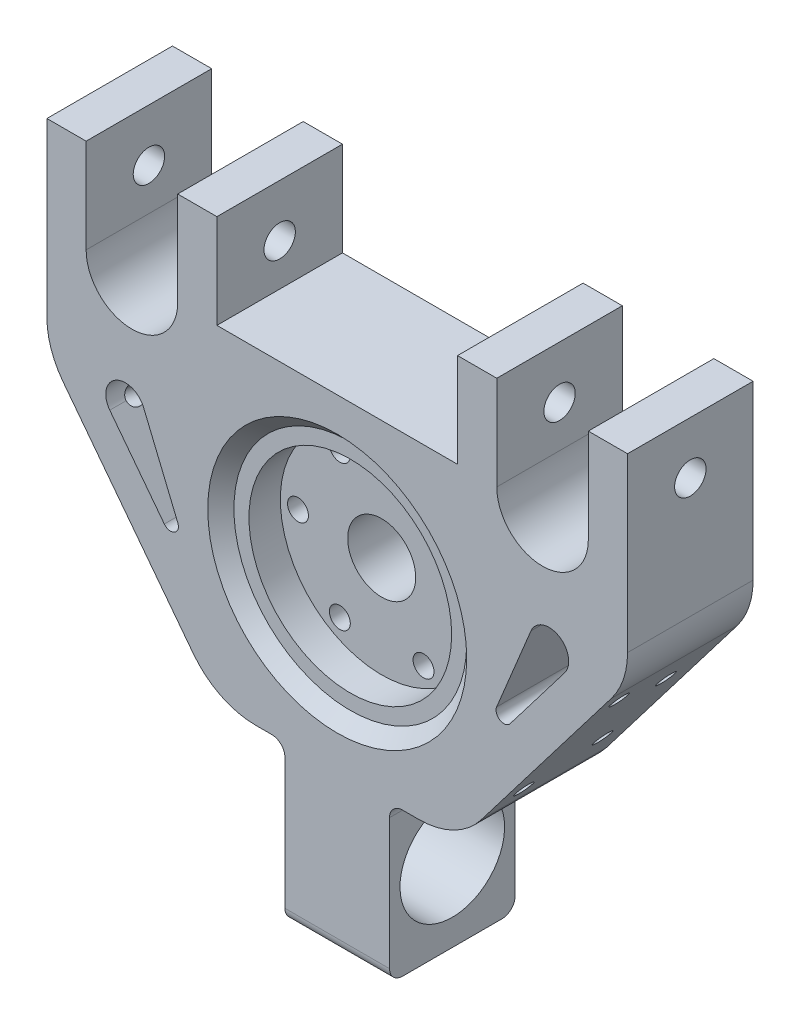
SolidWorks part; units mm, degrees
material "7075-O (SS)"
ref_plane "Płaszczyzna przednia" through (0, 0, 0) normal (0, 0, 1) x (1, 0, 0)
ref_plane "Płaszczyzna górna" through (0, 0, 0) normal (0, 1, 0) x (1, 0, 0)
ref_plane "Płaszczyzna prawa" through (0, 0, 0) normal (1, 0, 0) x (0, 0, -1)
sketch "Szkic1" plane through (0, 0, 0) normal (0, 0, 1) x (1, 0, 0)
  line L1 (-111, -62.5) -> (111, -62.5)
  line L2 (-111, -62.5) -> (-111, 62.5)
  line L3 (-111, 62.5) -> (111, 62.5)
  line L4 (111, -62.5) -> (111, 62.5)
  line L5 (-111, -62.5) -> (111, 62.5) construction
  line L6 (-111, 62.5) -> (111, -62.5) construction
  circle A0 centre (0, 0) radius 13
  circle A1 centre (-32, 0) radius 4
  circle A2 centre (-16, 27.7128) radius 4
  circle A3 centre (16, 27.7128) radius 4
  circle A4 centre (32, 0) radius 4
  circle A5 centre (16, -27.7128) radius 4
  circle A6 centre (-16, -27.7128) radius 4
  point P0 (0, 0)
  point P22 (0, 0)
  point P23 (0, 0)
  dimension "D3" = 26
  dimension "D4" = 8
  dimension "D5" = 32
  dimension "D2" = 222
  dimension "12" = 125
  dimension "D9" = 32
  dimension "D6" = 6
extrude "Dodanie-wyciągnięcie1" add sketch "Szkic1" along normal blind 13.5 and the other way blind 13.5
sketch "Szkic4" plane through (0, 62.5, 0) normal (0, 1, 0) x (1, 0, 0)
  line L0 (111, -13.5) -> (-111, -13.5) construction
  line L1 (-111, 13.5) -> (-96, 13.5)
  line L2 (-111, 13.5) -> (-111, -13.5)
  line L3 (-111, -13.5) -> (-96, -13.5)
  line L4 (-96, 13.5) -> (-96, -13.5)
  line L5 (111, 13.5) -> (-111, 13.5) construction
  line L6 (-61, 13.5) -> (-46, 13.5)
  line L7 (-61, 13.5) -> (-61, -13.5)
  line L8 (-61, -13.5) -> (-46, -13.5)
  line L9 (-46, 13.5) -> (-46, -13.5)
  line L11 (46, 13.5) -> (61, 13.5)
  line L12 (46, 13.5) -> (46, -13.5)
  line L13 (46, -13.5) -> (61, -13.5)
  line L14 (61, 13.5) -> (61, -13.5)
  line L15 (111, 13.5) -> (96, 13.5)
  line L16 (111, 13.5) -> (111, -13.5)
  line L17 (111, -13.5) -> (96, -13.5)
  line L18 (96, 13.5) -> (96, -13.5)
  dimension "D1" = 15
  dimension "D2" = 15
  dimension "D3" = 15
  dimension "D4" = 15
  dimension "D5" = 35
  dimension "D6" = 35
extrude "Dodanie-wyciągnięcie4" add sketch "Szkic4" along normal blind 36
sketch "Szkic13" plane through (0, 0, 13.5) normal (0, 0, 1) x (1, 0, 0)
  circle A0 centre (0, 0) radius 38.75
  circle A1 centre (0, 0) radius 13 construction
  dimension "D1" = 77.5
extrude "Wytnij-wyciągnięcie4" cut sketch "Szkic13" against normal blind 17 contours A0
sketch "Szkic15" plane through (0, 0, 13.5) normal (0, 0, 1) x (1, 0, 0)
  circle A0 centre (0, 0) radius 44.5
  circle A1 centre (0, 0) radius 38.75 construction
  dimension "D1" = 89
extrude "Wytnij-wyciągnięcie5" cut sketch "Szkic15" against normal blind 5
draft "Pochylenie1" type of draft neutral plane draft angle 45 faces to draft 1 face at (44.5, 0, 8.5) neutral plane through (0, 0, 8.5) neutral plane normal (0, 0, 1) parameters "D1"=45
sketch "Szkic16" plane through (0, 0, -13.5) normal (0, 0, -1) x (-1, 0, 0)
  line L18 (-111, 98.5) -> (-111, -62.5)
  line L19 (-111, -62.5) -> (111, -62.5)
  line L22 (111, -62.5) -> (111, 98.5)
  line L23 (111, 98.5) -> (96, 98.5)
  line L24 (96, 98.5) -> (96, 62.5)
  line L25 (96, 62.5) -> (61, 62.5)
  line L26 (61, 62.5) -> (61, 98.5)
  line L27 (61, 98.5) -> (46, 98.5)
  line L28 (46, 98.5) -> (46, 62.5)
  line L29 (46, 62.5) -> (-46, 62.5)
  line L30 (-46, 62.5) -> (-46, 98.5)
  line L31 (-46, 98.5) -> (-61, 98.5)
  line L32 (-61, 98.5) -> (-61, 62.5)
  line L33 (-61, 62.5) -> (-96, 62.5)
  line L34 (-96, 62.5) -> (-96, 98.5)
  line L35 (-96, 98.5) -> (-111, 98.5)
  line L36 (-111, 98.5) -> (-111, -62.5)
  line L37 (-111, -62.5) -> (111, -62.5)
  line L40 (111, -62.5) -> (111, 98.5)
  line L41 (111, 98.5) -> (96, 98.5)
  line L42 (96, 98.5) -> (96, 62.5)
  line L43 (96, 62.5) -> (61, 62.5)
  line L44 (61, 62.5) -> (61, 98.5)
  line L45 (61, 98.5) -> (46, 98.5)
  line L46 (46, 98.5) -> (46, 62.5)
  line L47 (46, 62.5) -> (-46, 62.5)
  line L48 (-46, 62.5) -> (-46, 98.5)
  line L49 (-46, 98.5) -> (-61, 98.5)
  line L50 (-61, 98.5) -> (-61, 62.5)
  line L51 (-61, 62.5) -> (-96, 62.5)
  line L52 (-96, 62.5) -> (-96, 98.5)
  line L53 (-96, 98.5) -> (-111, 98.5)
  circle A1 centre (0, 0) radius 13
  circle A2 centre (0, 0) radius 13
  circle A3 centre (32, 0) radius 4
  circle A4 centre (32, 0) radius 4
  circle A5 centre (16, 27.7128) radius 4
  circle A6 centre (16, 27.7128) radius 4
  circle A7 centre (-16, 27.7128) radius 4
  circle A8 centre (-16, 27.7128) radius 4
  circle A9 centre (-32, 0) radius 4
  circle A10 centre (-32, 0) radius 4
  circle A11 centre (-16, -27.7128) radius 4
  circle A12 centre (-16, -27.7128) radius 4
  circle A13 centre (16, -27.7128) radius 4
  circle A14 centre (16, -27.7128) radius 4
  dimension "D1" = 0
  dimension "D2" = 0
  dimension "D3" = 0
  dimension "D4" = 0
  dimension "D5" = 0
  dimension "D6" = 0
  dimension "D7" = 0
  dimension "D8" = 0
extrude "Dodanie-wyciągnięcie6" add sketch "Szkic16" along normal blind 21
sketch "Szkic5" plane through (-111, 0, 0) normal (-1, 0, 0) x (0, 0, 1)
  line L0 (13.5, 98.5) -> (13.5, -62.5) construction
  line L2 (-34.5, 98.5) -> (13.5, 98.5) construction
  circle A0 centre (-10.5, 78.5) radius 6
  dimension "D1" = 12
  dimension "D2" = 24
  dimension "D3" = 20
extrude "Wytnij-wyciągnięcie3" cut sketch "Szkic5" against normal through all contours A0
sketch "Szkic18" plane through (0, 0, -34.5) normal (0, 0, -1) x (-1, 0, 0)
  line L2 (111, 22.5) -> (46, -62.5)
  line L3 (111, -62.5) -> (111, 98.5) construction
  line L4 (-111, -62.5) -> (111, -62.5) construction
  line L5 (111, 22.5) -> (111, -62.5)
  line L6 (111, -62.5) -> (46, -62.5)
  line L7 (-111, -62.5) -> (-46, -62.5)
  line L8 (-46, -62.5) -> (-111, 22.5)
  line L9 (-111, 98.5) -> (-111, -62.5) construction
  line L10 (-111, 22.5) -> (-111, -62.5)
  dimension "D1" = 65
  dimension "D2" = 85
extrude "Wytnij-wyciągnięcie6" cut sketch "Szkic18" against normal through all
fillet "Zaokrąglenie1" radius 30 1 edges at (-111, 22.5, -10.5)
fillet "Zaokrąglenie2" radius 30 3 edges at (111, 22.5, -10.5) (46, -62.5, -10.5) (-46, -62.5, -10.5)
sketch "Szkic19" plane through (0, 0, -34.5) normal (0, 0, -1) x (-1, 0, 0)
  line L5 (-31.1748, -62.5) -> (31.1748, -62.5) construction
  line L6 (-20, -62.5) -> (20, -62.5)
  line L7 (-20, -62.5) -> (-20, -122.5)
  line L8 (-20, -122.5) -> (20, -122.5)
  line L9 (20, -62.5) -> (20, -122.5)
  point P4 (0, -62.5)
  dimension "D1" = 40
  dimension "D2" = 60
extrude "Dodanie-wyciągnięcie7" add sketch "Szkic19" against normal up to surface (48 mm away) up to face at (-49.5, 0, 13.5)
sketch "Szkic23" plane through (20, 0, 0) normal (1, 0, 0) x (0, 0, -1)
  line L0 (-13.5, -122.5) -> (34.5, -122.5) construction
  circle A0 centre (10.5, -92.5) radius 20
  point P5 (10.5, -122.5)
  dimension "D1" = 40
  dimension "D2" = 30
extrude "Wytnij-wyciągnięcie7" cut sketch "Szkic23" against normal up to next
sketch "Szkic24" plane through (0, 0, -34.5) normal (0, 0, -1) x (-1, 0, 0)
  line L0 (-96, 62.5) -> (-61, 62.5)
  line L1 (61, 62.5) -> (96, 62.5)
  line L2 (-96, 62.5) -> (-96, 98.5) construction
  line L3 (61, 62.5) -> (61, 98.5) construction
  arc A0 (-96, 62.5) -> (-61, 62.5) centre (-78.5, 62.5) ccw
  arc A1 (61, 62.5) -> (96, 62.5) centre (78.5, 62.5) ccw
extrude "Wytnij-wyciągnięcie8" cut sketch "Szkic24" against normal up to next
fillet "Zaokrąglenie4" radius 5 2 edges at (20, -62.5, -10.5) (-20, -62.5, -10.5)
fillet "Zaokrąglenie5" radius 5 2 edges at (0, -122.5, -34.5) (0, -122.5, 13.5)
sketch "Szkic25" plane through (0, 0, 13.5) normal (0, 0, 1) x (1, 0, 0)
  line L0 (-60.9515, -10.3535) -> (-74.0693, 21.3662)
  line L1 (-66.1069, -13.3224) -> (-86.9577, 13.9441)
  line L2 (0, 0) -> (0, 65.4939) construction
  line L3 (66.1069, -13.3224) -> (86.9577, 13.9441)
  line L4 (-111, 98.5) -> (-111, 32.656) construction
  line L5 (-61, 98.5) -> (-46, 98.5) construction
  line L6 (60.9515, -10.3535) -> (74.0693, 21.3662)
  line L7 (-104.8307, 14.4325) -> (-55.0056, -50.7235) construction
  arc A0 (-74.0693, 21.3662) -> (-86.9577, 13.9441) centre (-81, 18.5) ccw
  arc A13 (-66.1069, -13.3224) -> (-60.9515, -10.3535) centre (-63.7238, -11.5) ccw
  arc A14 (66.1069, -13.3224) -> (60.9515, -10.3535) centre (63.7238, -11.5) cw
  arc A15 (74.0693, 21.3662) -> (86.9577, 13.9441) centre (81, 18.5) cw
  dimension "D1" = 30
  dimension "D2" = 80
  dimension "D6" = 6
  dimension "D5" = 15
  dimension "D4" = 110
extrude "Wytnij-wyciągnięcie9" cut sketch "Szkic25" against normal up to surface (48 mm away) up to face at (0, 17.7221, -34.5)
hole_wizard "Otwór gwintowany M81" positions "Szkic27" profile "Szkic28" tap size "M8" standard "ISO"
sketch "Szkic27" plane through (-59.1845, -45.2587, 0) normal (-0.7944, -0.6075, 0) x (0, 0, 1)
  line L0 (-34.5, 75.144) -> (-34.5, -6.8795) construction
  line L1 (-10.5, 22.8237) -> (-10.5, 73.239) construction
  line L3 (16.7871, 34.1323) -> (-56.7075, 34.1323) construction
  line L5 (13.5, 75.144) -> (13.5, -6.8795) construction
  line L6 (13.5, 75.144) -> (-34.5, 75.144) construction
  line L7 (-34.5, -6.8795) -> (13.5, -6.8795) construction
  point P0 (-20.15, 54.1323)
  point P6 (3.85, 64.1323)
  dimension "D1" = 14.35
  dimension "D2" = 20
  dimension "D3" = 30
  dimension "D4" = 9.65
sketch "Szkic28" plane through (-92.0671, -2.2583, -20.15) normal (0, 0, 1) x (0.6075, -0.7944, 0)
  line L0 (0, 0) -> (0, 47.0429)
  line L1 (0, 47.0429) -> (3.4, 45)
  line L2 (3.4, 45) -> (3.4, 0)
  line L5 (3.4, 0) -> (0, 0)
  line L10 (0, 47.0429) -> (-3.4, 45) construction
  line L11 (0, -6.35) -> (0, 107.95) construction
  dimension "Średnica wiertła gwintu" = 6.8
  dimension "Głębokość otworu gwintowanego" = 45
  dimension "Kąt wiertła" = 118
cosmetic thread "Gwint otworu1" parameters "D1"=37, "D2"=8
cosmetic thread "Gwint otworu4" parameters "D1"=37, "D2"=8
hole_wizard "Otwór gwintowany M82" positions "Szkic29" profile "Szkic30" tap size "M8" standard "ISO"
sketch "Szkic29" plane through (-59.1845, -45.2587, 0) normal (-0.7944, -0.6075, 0) x (0, 0, 1)
  line L0 (17.5076, 34.1323) -> (-50.8158, 34.1323) construction
  line L2 (13.5, 75.144) -> (-34.5, 75.144) construction
  line L3 (-34.5, -6.8795) -> (13.5, -6.8795) construction
  point P0 (3.85, 4.1323)
  point P2 (-20.15, 14.1323)
  dimension "D1" = 20
  dimension "D2" = 30
sketch "Szkic30" plane through (-61.6946, -41.9762, 3.85) normal (0, 0, 1) x (0.6075, -0.7944, 0)
  line L0 (0, 0) -> (0, 27.0429)
  line L1 (0, 27.0429) -> (3.4, 25)
  line L2 (3.4, 25) -> (3.4, 0)
  line L5 (3.4, 0) -> (0, 0)
  line L10 (0, 27.0429) -> (-3.4, 25) construction
  line L11 (0, -6.35) -> (0, 107.95) construction
  dimension "Średnica wiertła gwintu" = 6.8
  dimension "Głębokość otworu gwintowanego" = 25
  dimension "Kąt wiertła" = 118
cosmetic thread "Gwint otworu5" parameters "D1"=17, "D2"=8
cosmetic thread "Gwint otworu6" parameters "D1"=17, "D2"=8
mirror "Lustro1" about plane through (0, 0, 0) normal (1, 0, 0) of "Otwór gwintowany M82", "Otwór gwintowany M81"
cosmetic thread "Gwint otworu7" parameters "D1"=37, "D2"=8
cosmetic thread "Gwint otworu8" parameters "D1"=17, "D2"=8
cosmetic thread "Gwint otworu9" parameters "D1"=17, "D2"=8
